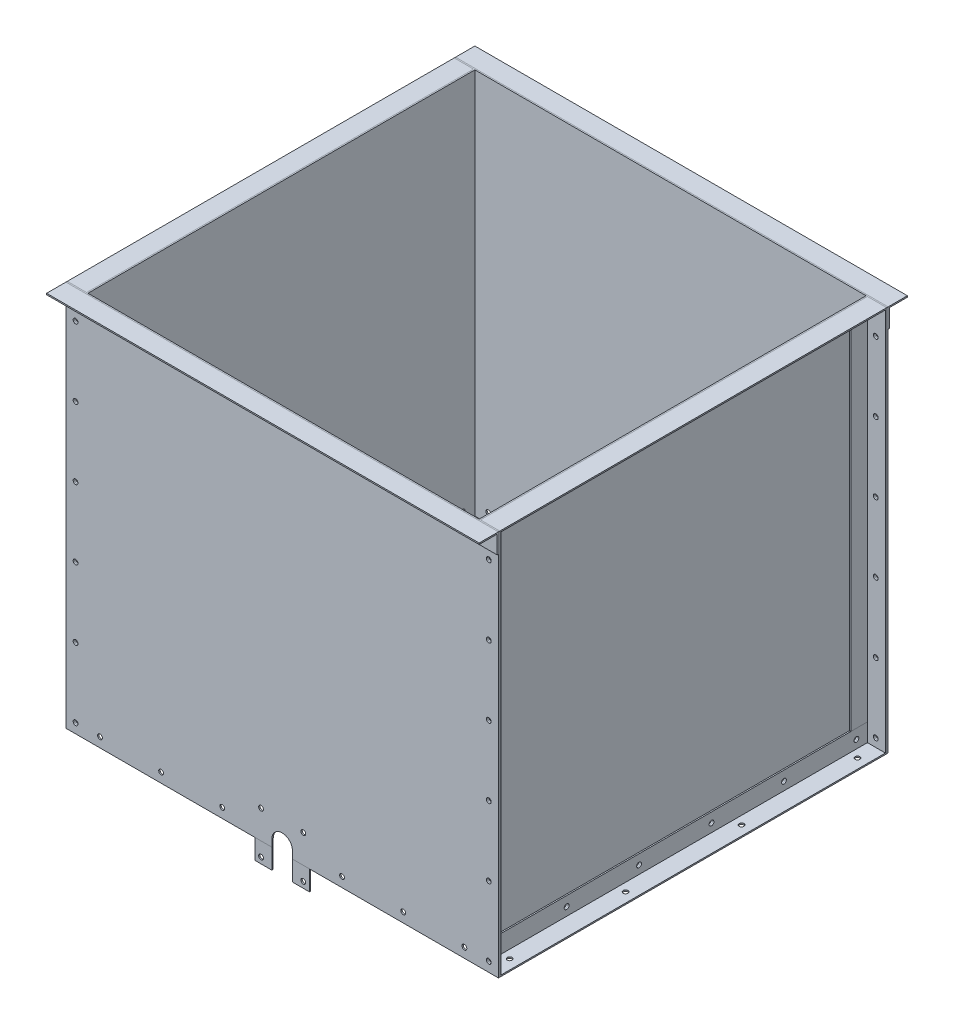
SolidWorks part; units mm, degrees
ref_plane "Plano frontal" through (0, 0, 0) normal (0, 0, 1) x (1, 0, 0)
ref_plane "Plano superior" through (0, 0, 0) normal (0, 1, 0) x (1, 0, 0)
ref_plane "Plano direito" through (0, 0, 0) normal (1, 0, 0) x (0, 0, -1)
sketch "Esboço1" plane through (0, 0, 0) normal (0, 0, 1) x (1, 0, 0)
  line L0 (0, 0) -> (0, 1227.36) construction
  line L1 (568.65, -19.05) -> (568.65, 996.95)
  line L2 (568.65, 996.95) -> (-568.65, 996.95)
  line L3 (568.65, -19.05) -> (27, -19.05)
  line L4 (-568.65, -19.05) -> (-568.65, 996.95)
  line L5 (-27, 0) -> (-27, -19.05)
  line L6 (27, 0) -> (27, -19.05)
  line L7 (543.25, 996.95) -> (543.25, -19.05) construction
  line L8 (-27, -19.05) -> (-568.65, -19.05)
  line L9 (-543.25, 996.95) -> (-543.25, -19.05) construction
  line L10 (543.25, 6.35) -> (-543.25, 6.35) construction
  arc A0 (27, 0) -> (-27, 0) centre (0, 0) ccw
  circle A1 centre (157.536, 6.35) radius 6.35
  circle A2 centre (318.318, 6.35) radius 6.35
  circle A3 centre (479.1, 6.35) radius 6.35
  circle A4 centre (-479.1, 6.35) radius 6.35
  circle A5 centre (-318.318, 6.35) radius 6.35
  circle A6 centre (-157.536, 6.35) radius 6.35
  circle A7 centre (543.25, 6.35) radius 6.35
  circle A8 centre (543.25, 189.23) radius 6.35
  circle A9 centre (543.25, 372.11) radius 6.35
  circle A10 centre (543.25, 554.99) radius 6.35
  circle A11 centre (543.25, 737.87) radius 6.35
  circle A12 centre (543.25, 920.75) radius 6.35
  circle A13 centre (-543.25, 920.75) radius 6.35
  circle A14 centre (-543.25, 737.87) radius 6.35
  circle A15 centre (-543.25, 554.99) radius 6.35
  circle A16 centre (-543.25, 372.11) radius 6.35
  circle A17 centre (-543.25, 189.23) radius 6.35
  circle A18 centre (-543.25, 6.35) radius 6.35
  dimension "D3" = 12.7
  dimension "D4" = 12.7
  dimension "D5" = 12.7
  dimension "D6" = 12.7
  dimension "D7" = 12.7
  dimension "D14" = 27
  dimension "D18" = 25.4
  dimension "D1" = 1016
  dimension "D2" = 25.4
  dimension "D8" = 182.88
  dimension "D9" = 182.88
  dimension "D10" = 182.88
  dimension "D11" = 182.88
  dimension "D12" = 182.88
  dimension "D13" = 19.05
  dimension "D15" = 19.05
  dimension "D16" = 19.05
  dimension "D17" = 568.65
  dimension "D19" = 25.4
  dimension "D20" = 64.15
  dimension "D21" = 224.932
  dimension "D22" = 385.714
base flange "Flange-base1" sketch "Esboço1" thickness 3.5 reverse thickness direction no parameters "D1"=6
pattern_linear "Padrão linear1" count 2 spacing 1021 along (0, 0, -1) of bodies 101
sketch "Esboço8" plane through (0, 996.95, 0) normal (0, 1, 0) x (1, 0, 0)
  line L0 (568.65, 1021) -> (-568.65, 1021) construction
  line L1 (517.85, 1021) -> (514.35, 1021)
  line L2 (517.85, 1021) -> (517.85, 3.5)
  line L3 (517.85, 3.5) -> (514.35, 3.5)
  line L4 (514.35, 1021) -> (514.35, 3.5)
  line L5 (568.65, 3.5) -> (-568.65, 3.5) construction
  line L6 (568.65, 3.5) -> (568.65, 0) construction
  line L7 (0, 0) -> (0, 1373.5489) construction
  line L8 (-514.35, 1021) -> (-514.35, 3.5)
  line L9 (-517.85, 3.5) -> (-514.35, 3.5)
  line L10 (-517.85, 1021) -> (-517.85, 3.5)
  line L11 (-517.85, 1021) -> (-514.35, 1021)
  dimension "D1" = 3.5
  dimension "D2" = 50.8
extrude "Ressalto-extrusão1" add sketch "Esboço8" against normal up to surface (1016 mm away) up to face at (297.825, -19.05, -1022.75)
sketch "Esboço11" plane through (0, 0, -1021) normal (0, 0, 1) x (1, 0, 0)
  line L0 (517.85, 31.75) -> (521.35, 31.75)
  line L1 (517.85, -19.05) -> (517.85, 996.95) construction
  line L2 (521.35, 31.75) -> (521.35, -15.55)
  line L3 (521.35, -15.55) -> (568.65, -15.55)
  line L4 (568.65, -19.05) -> (568.65, 996.95) construction
  line L5 (568.65, -15.55) -> (568.65, -19.05)
  line L6 (568.65, -19.05) -> (517.85, -19.05)
  line L7 (517.85, -19.05) -> (517.85, 31.75)
  dimension "D1" = 3.5
  dimension "D2" = 3.5
  dimension "D3" = 50.8
extrude "Ressalto-extrusão2" add sketch "Esboço11" along normal up to surface (1017.5 mm away) separate body up to face at (549.6, 920.75, -3.5)
sketch "Esboço12" plane through (521.35, 0, 0) normal (1, 0, 0) x (0, 0, -1)
  line L0 (512.25, 31.75) -> (512.25, -121.4216) construction
  line L1 (3.5, 31.75) -> (1021, 31.75) construction
  line L2 (3.5, 6.35) -> (1021, 6.35) construction
  line L4 (1021, -19.05) -> (1021, 996.95) construction
  line L5 (3.5, -19.05) -> (0, -19.05) construction
  circle A0 centre (417, 6.35) radius 6.35
  circle A1 centre (226.5, 6.35) radius 6.35
  circle A2 centre (36, 6.35) radius 6.35
  circle A3 centre (988.5, 6.35) radius 6.35
  circle A4 centre (798, 6.35) radius 6.35
  circle A5 centre (607.5, 6.35) radius 6.35
  dimension "D2" = 12.7
  dimension "D3" = 190.5
  dimension "D4" = 12.7
  dimension "D5" = 190.5
  dimension "D6" = 12.7
  dimension "D7" = 190.5
  dimension "D1" = 25.4
extrude "Corte-extrusão2" cut sketch "Esboço12" against normal blind 10
mirror "Espelhar2" about plane through (0, 0, 0) normal (1, 0, 0) of "Corte-extrusão2", "Ressalto-extrusão2"
sketch "Esboço13" plane through (0, 996.95, 0) normal (0, 1, 0) x (1, 0, 0)
  line L0 (568.65, 512.25) -> (-568.65, 512.25) construction
  line L1 (517.85, 1021) -> (521.35, 1021)
  line L2 (517.85, 1021) -> (517.85, 973.7)
  line L3 (517.85, 973.7) -> (521.35, 973.7)
  line L4 (521.35, 1021) -> (521.35, 973.7)
  line L5 (568.65, 3.5) -> (568.65, 1021) construction
  line L6 (-568.65, 3.5) -> (-568.65, 1021) construction
  line L7 (521.35, 3.5) -> (521.35, 50.8)
  line L8 (517.85, 50.8) -> (521.35, 50.8)
  line L9 (517.85, 3.5) -> (517.85, 50.8)
  line L10 (517.85, 3.5) -> (521.35, 3.5)
  dimension "D1" = 3.5
  dimension "D2" = 47.3
extrude "Ressalto-extrusão4" add sketch "Esboço13" against normal up to surface (965.2 mm away) separate body up to face at (519.6, 31.75, -512.25)
mirror "Espelhar3" about plane through (0, 0, 0) normal (1, 0, 0) of "Ressalto-extrusão4"
sketch "Esboço14" plane through (568.65, 0, 0) normal (1, 0, 0) x (0, 0, -1)
  line L0 (0, 996.95) -> (0, 946.15)
  line L1 (0, -19.05) -> (0, 996.95) construction
  line L2 (0, 996.95) -> (-50.8, 996.95)
  line L3 (-3.5, 993.45) -> (-3.5, 946.15)
  line L4 (-3.5, 993.45) -> (-50.8, 993.45)
  line L5 (0, 946.15) -> (-3.5, 946.15)
  line L6 (-50.8, 996.95) -> (-50.8, 993.45)
  dimension "D1" = 50.8
  dimension "D2" = 50.8
  dimension "D3" = 3.5
extrude "Ressalto-extrusão5" add sketch "Esboço14" against normal up to surface (1137.3 mm away) separate body up to face at (-568.65, 489.825, -512.25)
sketch "Esboço15" plane through (0, 0, -3.5) normal (0, 0, -1) x (-1, 0, 0)
  line L0 (-517.85, 996.95) -> (-568.65, 996.95)
  line L1 (-517.85, 996.95) -> (-517.85, 946.15)
  line L2 (-517.85, -19.05) -> (-517.85, 996.95) construction
  line L3 (568.65, 946.15) -> (-568.65, 946.15) construction
  line L4 (-517.85, 946.15) -> (-521.35, 946.15)
  line L5 (-521.35, 31.75) -> (-521.35, 996.95) construction
  line L6 (-521.35, 946.15) -> (-521.35, 993.45)
  line L7 (568.65, 993.45) -> (-568.65, 993.45) construction
  line L8 (-521.35, 993.45) -> (-568.65, 993.45)
  line L9 (-568.65, 993.45) -> (-568.65, 996.95)
extrude "Ressalto-extrusão6" add sketch "Esboço15" along normal up to surface (1017.5 mm away) separate body up to face at (549.6, 920.75, -1021)
sketch "Esboço16" plane through (521.35, 0, 0) normal (1, 0, 0) x (0, 0, -1)
  line L0 (1021, -19.05) -> (1021, 996.95) construction
  line L1 (3.5, 996.95) -> (1021, 996.95)
  line L2 (3.5, 996.95) -> (3.5, 946.15)
  line L3 (3.5, 946.15) -> (1021, 946.15)
  line L4 (1021, 996.95) -> (1021, 946.15)
  dimension "D1" = 50.8
extrude "Corte-extrusão3" cut sketch "Esboço16" against normal blind 3.5
sketch "Esboço17" plane through (-521.35, 0, 0) normal (-1, 0, 0) x (0, 0, 1)
  line L4 (-3.5, 996.95) -> (-1021, 996.95)
  line L5 (-1021, 996.95) -> (-1021, 946.15)
  line L6 (-1021, 946.15) -> (-3.5, 946.15)
  line L7 (-3.5, 946.15) -> (-3.5, 996.95)
  line L8 (-3.5, 996.95) -> (-1021, 996.95)
  line L9 (-1021, 996.95) -> (-1021, 946.15)
  line L10 (-1021, 946.15) -> (-3.5, 946.15)
  line L11 (-3.5, 946.15) -> (-3.5, 996.95)
  dimension "D1" = 0
extrude "Corte-extrusão4" cut sketch "Esboço17" against normal blind 3.5
mirror "Espelhar7" about plane through (0, 0, 0) normal (1, 0, 0) of bodies 115
ref_plane "Plano1" through (0, 0, -512.25) normal (0, 0, 1) x (1, 0, 0)
mirror "Espelhar8" about plane through (0, 0, -512.25) normal (0, 0, 1) of bodies 114
sketch "Esboço18" plane through (0, 0, -3.5) normal (0, 0, -1) x (-1, 0, 0)
  line L0 (-521.35, 993.45) -> (-568.65, 993.45)
  line L1 (-521.35, 993.45) -> (-521.35, -15.55)
  line L2 (-521.35, -15.55) -> (-521.35, 31.75) construction
  line L3 (-568.65, -15.55) -> (-521.35, -15.55)
  line L4 (-568.65, -19.05) -> (-517.85, -19.05)
  line L5 (-517.85, -19.05) -> (-517.85, 996.95)
  line L6 (-517.85, 996.95) -> (-568.65, 996.95)
  line L7 (-568.65, 996.95) -> (-568.65, -19.05)
  line L11 (-568.65, 993.45) -> (-568.65, -15.55)
  circle A0 centre (-543.25, 6.35) radius 6.35 construction
  circle A1 centre (-543.25, 189.23) radius 6.35 construction
  circle A2 centre (-543.25, 372.11) radius 6.35 construction
  circle A3 centre (-543.25, 554.99) radius 6.35 construction
  circle A4 centre (-543.25, 737.87) radius 6.35 construction
  circle A5 centre (-543.25, 920.75) radius 6.35 construction
  circle A6 centre (-543.25, 6.35) radius 6.35
  circle A7 centre (-543.25, 189.23) radius 6.35
  circle A8 centre (-543.25, 372.11) radius 6.35
  circle A9 centre (-543.25, 554.99) radius 6.35
  circle A10 centre (-543.25, 737.87) radius 6.35
  circle A11 centre (-543.25, 920.75) radius 6.35
  dimension "D1" = 0
extrude "Ressalto-extrusão7" add sketch "Esboço18" along normal blind 3.5 separate body
mirror "Espelhar9" about plane through (0, 0, -512.25) normal (0, 0, 1) of bodies 121
ref_plane "Plano2" through (0, 0, 0) normal (-1, 0, 0) x (0, 0, 1)
mirror "Espelhar10" about plane through (0, 0, 0) normal (-1, 0, 0) of bodies 121 122
sketch "Esboço19" plane through (0, -15.55, 0) normal (0, 1, 0) x (1, 0, 0)
  line L0 (-565.65, 359.849) -> (-520.85, 359.849) construction
  line L1 (0, 1089.75) -> (0, -570.8205) construction
  line L2 (25.4, 1089.75) -> (-25.4, 1089.75) construction
  circle A0 centre (-543.25, 969.45) radius 6.35
  circle A1 centre (-543.25, 664.651) radius 6.351
  circle A2 centre (-543.25, 359.849) radius 6.351
  circle A3 centre (-543.25, 55.05) radius 6.35
  circle A4 centre (543.25, 55.05) radius 6.35
  circle A5 centre (543.25, 359.849) radius 6.351
  circle A6 centre (543.25, 664.651) radius 6.351
  circle A7 centre (543.25, 969.45) radius 6.35
  dimension "D1" = 12.7
  dimension "D2" = 12.702
  dimension "D3" = 12.702
  dimension "D4" = 12.7
extrude "Corte-extrusão5" cut sketch "Esboço19" against normal up to surface (3.5 mm away) up to face at (543.25, -19.05, -512.25)
sketch "Esboço20" plane through (0, 0, 0) normal (0, 0, 1) x (1, 0, 0)
  circle A0 centre (-55.5623, 55.5623) radius 6.35
  circle A1 centre (55.5623, 55.5623) radius 6.35
  dimension "D1" = 12.7
  dimension "D2" = 12.7
extrude "Corte-extrusão6" cut sketch "Esboço20" against normal blind 10
sketch "Esboço22" plane through (0, 0, 0) normal (0, 0, 1) x (1, 0, 0)
  line L0 (0, 0) -> (0, -150.4853) construction
  line L1 (-568.65, -19.05) -> (-27, -19.05) construction
  line L2 (-71.4377, -19.05) -> (-27, -19.05)
  line L3 (-71.4377, -19.05) -> (-71.4377, -71.4377)
  line L4 (-71.4377, -71.4377) -> (-27, -71.4377)
  line L5 (71.4373, -19.05) -> (71.4373, -71.4377) construction
  line L6 (71.4373, 55.5623) -> (71.4373, -55.5627) construction
  line L8 (-71.4377, -55.5627) -> (-71.4377, 55.5623) construction
  line L9 (55.5623, -71.4377) -> (-55.5627, -71.4377) construction
  line L10 (27, -19.05) -> (27, -71.4377) construction
  line L11 (-27, -19.05) -> (-27, -71.4377)
  line L12 (27, -71.4377) -> (71.4373, -71.4377) construction
  line L13 (27, -19.05) -> (71.4373, -19.05) construction
  circle A0 centre (55.5623, -55.5627) radius 6.35 construction
  circle A1 centre (-55.5623, -55.5623) radius 6.35
  dimension "D1" = 12.7
  dimension "D2" = 12.7
base flange "Aba1" sketch "Esboço22" thickness 3.5 reverse thickness direction no parameters "D1"=6
mirror "Espelhar11" about plane through (0, 0, 0) normal (1, 0, 0) of bodies 129
mirror "Espelhar12" about plane through (0, 0, -512.25) normal (0, 0, 1) of bodies 129 130
sketch "Esboço31" plane through (0, 0, -1024.5) normal (0, 0, -1) x (-1, 0, 0)
  circle A0 centre (55.5625, 55.5625) radius 6.35
  circle A1 centre (-55.5625, 55.5625) radius 6.35
  dimension "D1" = 12.7
  dimension "D2" = 12.7
extrude "Corte-extrusão7" cut sketch "Esboço31" against normal up to surface (1024.5 mm away) up to face at (-49.2123, 55.5623, 0)
sketch "Curva-Linhas1" [suppressed] plane through (0, 0, 0) normal (0, 1, 0) x (1, 0, 0)
sketch "Caixa delimitadora1" [suppressed] plane through (0, 0, 0) normal (0, 1, 0) x (1, 0, 0)
sheet metal parameters "Chapa metálica1" thickness 3.5 parameters "D1"=6
flat pattern "Padrão-Plano1" [suppressed]
sketch "Curva-Linhas2" plane through (0, 0, 0) normal (0, 1, 0) x (1, 0, 0)
sketch3d "Caixa delimitadora2" [suppressed]
  line L0 (568.65, -19.05, 0) -> (-568.65, -19.05, 0) construction
  line L1 (568.65, 996.95, 0) -> (-568.65, 996.95, 0) construction
  line L2 (568.65, -19.05, 0) -> (568.65, 996.95, 0) construction
  line L3 (-568.65, -19.05, 0) -> (-568.65, 996.95, 0) construction
sheet metal parameters "Chapa metálica2" thickness 3.5 parameters "D1"=6
flat pattern "Padrão-Plano2"
sketch "Curva-Linhas3" plane through (0, 0, 0) normal (0, 1, 0) x (1, 0, 0)
sketch "Caixa delimitadora3" [suppressed] plane through (0, 0, 0) normal (0, 1, 0) x (1, 0, 0)
sheet metal parameters "Chapa metálica3" thickness 3.5 parameters "D1"=6
flat pattern "Padrão-Plano3"
sketch "Curva-Linhas4" plane through (0, 0, 0) normal (0, 1, 0) x (1, 0, 0)
sketch3d "Caixa delimitadora4" [suppressed]
  line L0 (-568.65, -19.05, 0) -> (568.65, -19.05, 0) construction
  line L1 (-568.65, 996.95, 0) -> (568.65, 996.95, 0) construction
  line L2 (-568.65, -19.05, 0) -> (-568.65, 996.95, 0) construction
  line L3 (568.65, -19.05, 0) -> (568.65, 996.95, 0) construction
sheet metal parameters "Chapa metálica4" thickness 3.5 parameters "D1"=6
flat pattern "Padrão-Plano3"
sketch "Curva-Linhas4" plane through (0, 0, 0) normal (0, 1, 0) x (1, 0, 0)
sketch3d "Caixa delimitadora4" [suppressed]
  line L0 (-568.65, -19.05, 0) -> (568.65, -19.05, 0) construction
  line L1 (-568.65, 996.95, 0) -> (568.65, 996.95, 0) construction
  line L2 (-568.65, -19.05, 0) -> (-568.65, 996.95, 0) construction
  line L3 (568.65, -19.05, 0) -> (568.65, 996.95, 0) construction
sheet metal parameters "Chapa metálica7" thickness 3.5 parameters "D1"=6
flat pattern "Padrão-Plano3"
sketch "Curva-Linhas4" plane through (0, 0, 0) normal (0, 1, 0) x (1, 0, 0)
sketch3d "Caixa delimitadora4" [suppressed]
  line L0 (-568.65, -19.05, 0) -> (568.65, -19.05, 0) construction
  line L1 (-568.65, 996.95, 0) -> (568.65, 996.95, 0) construction
  line L2 (-568.65, -19.05, 0) -> (-568.65, 996.95, 0) construction
  line L3 (568.65, -19.05, 0) -> (568.65, 996.95, 0) construction
sheet metal parameters "Chapa metálica9" thickness 3.5 parameters "D1"=6
flat pattern "Padrão-Plano3"
sketch "Curva-Linhas4" plane through (0, 0, 0) normal (0, 1, 0) x (1, 0, 0)
sketch3d "Caixa delimitadora4" [suppressed]
  line L0 (-568.65, -19.05, 0) -> (568.65, -19.05, 0) construction
  line L1 (-568.65, 996.95, 0) -> (568.65, 996.95, 0) construction
  line L2 (-568.65, -19.05, 0) -> (-568.65, 996.95, 0) construction
  line L3 (568.65, -19.05, 0) -> (568.65, 996.95, 0) construction
sheet metal parameters "Chapa metálica10" thickness 3.5 parameters "D1"=6
flat pattern "Padrão-Plano3"
sketch "Curva-Linhas4" plane through (0, 0, 0) normal (0, 1, 0) x (1, 0, 0)
sketch3d "Caixa delimitadora4" [suppressed]
  line L0 (-568.65, -19.05, 0) -> (568.65, -19.05, 0) construction
  line L1 (-568.65, 996.95, 0) -> (568.65, 996.95, 0) construction
  line L2 (-568.65, -19.05, 0) -> (-568.65, 996.95, 0) construction
  line L3 (568.65, -19.05, 0) -> (568.65, 996.95, 0) construction
sheet metal parameters "Chapa metálica13" thickness 3.5 parameters "D1"=6
flat pattern "Padrão-Plano3"
sketch "Curva-Linhas4" plane through (0, 0, 0) normal (0, 1, 0) x (1, 0, 0)
sketch3d "Caixa delimitadora4" [suppressed]
  line L0 (-568.65, -19.05, 0) -> (568.65, -19.05, 0) construction
  line L1 (-568.65, 996.95, 0) -> (568.65, 996.95, 0) construction
  line L2 (-568.65, -19.05, 0) -> (-568.65, 996.95, 0) construction
  line L3 (568.65, -19.05, 0) -> (568.65, 996.95, 0) construction
sheet metal parameters "Chapa metálica18" thickness 3.5 parameters "D1"=6
flat pattern "Padrão-Plano3"
sketch "Curva-Linhas4" plane through (0, 0, 0) normal (0, 1, 0) x (1, 0, 0)
sketch3d "Caixa delimitadora4" [suppressed]
  line L0 (-568.65, -19.05, 0) -> (568.65, -19.05, 0) construction
  line L1 (-568.65, 996.95, 0) -> (568.65, 996.95, 0) construction
  line L2 (-568.65, -19.05, 0) -> (-568.65, 996.95, 0) construction
  line L3 (568.65, -19.05, 0) -> (568.65, 996.95, 0) construction
sheet metal parameters "Chapa metálica21" thickness 3.5 parameters "D1"=6
flat pattern "Padrão-Plano3"
sketch "Curva-Linhas4" plane through (0, 0, 0) normal (0, 1, 0) x (1, 0, 0)
sketch3d "Caixa delimitadora4" [suppressed]
  line L0 (-568.65, -19.05, 0) -> (568.65, -19.05, 0) construction
  line L1 (-568.65, 996.95, 0) -> (568.65, 996.95, 0) construction
  line L2 (-568.65, -19.05, 0) -> (-568.65, 996.95, 0) construction
  line L3 (568.65, -19.05, 0) -> (568.65, 996.95, 0) construction
sheet metal parameters "Chapa metálica26" thickness 3.5 parameters "D1"=6
flat pattern "Padrão-Plano3"
sketch "Curva-Linhas4" plane through (0, 0, 0) normal (0, 1, 0) x (1, 0, 0)
sketch3d "Caixa delimitadora4" [suppressed]
  line L0 (-568.65, -19.05, 0) -> (568.65, -19.05, 0) construction
  line L1 (-568.65, 996.95, 0) -> (568.65, 996.95, 0) construction
  line L2 (-568.65, -19.05, 0) -> (-568.65, 996.95, 0) construction
  line L3 (568.65, -19.05, 0) -> (568.65, 996.95, 0) construction
sheet metal parameters "Chapa metálica27" thickness 3.5 parameters "D1"=6
flat pattern "Padrão-Plano3"
sketch "Curva-Linhas4" plane through (0, 0, 0) normal (0, 1, 0) x (1, 0, 0)
sketch3d "Caixa delimitadora4" [suppressed]
  line L0 (-568.65, -19.05, 0) -> (568.65, -19.05, 0) construction
  line L1 (-568.65, 996.95, 0) -> (568.65, 996.95, 0) construction
  line L2 (-568.65, -19.05, 0) -> (-568.65, 996.95, 0) construction
  line L3 (568.65, -19.05, 0) -> (568.65, 996.95, 0) construction
sheet metal parameters "Chapa metálica29" thickness 3.5 parameters "D1"=6
flat pattern "Padrão-Plano29"
sketch "Curva-Linhas5" plane through (0, 0, 0) normal (0, 1, 0) x (1, 0, 0)
sketch3d "Caixa delimitadora5" [suppressed]
  line L0 (27, -19.05, 0) -> (27, -71.4377, 0) construction
  line L1 (71.4377, -19.05, 0) -> (71.4377, -71.4377, 0) construction
  line L2 (27, -19.05, 0) -> (71.4377, -19.05, 0) construction
  line L3 (27, -71.4377, 0) -> (71.4377, -71.4377, 0) construction
sheet metal parameters "Chapa metálica30" thickness 3.5 parameters "D1"=6
flat pattern "Padrão-Plano30"
sketch "Curva-Linhas6" plane through (0, 0, 0) normal (0, 1, 0) x (1, 0, 0)
sketch "Caixa delimitadora6" [suppressed] plane through (0, 0, 0) normal (0, 1, 0) x (1, 0, 0)
sheet metal parameters "Chapa metálica31" thickness 3.5 parameters "D1"=6
flat pattern "Padrão-Plano31"
sketch "Curva-Linhas7" plane through (0, 0, 0) normal (0, 1, 0) x (1, 0, 0)
sketch "Caixa delimitadora7" [suppressed] plane through (0, 0, 0) normal (0, 1, 0) x (1, 0, 0)
sheet metal parameters "Chapa metálica32" thickness 3.5 parameters "D1"=6
flat pattern "Padrão-Plano32"
sketch "Curva-Linhas8" plane through (0, 0, 0) normal (0, 1, 0) x (1, 0, 0)
sketch "Caixa delimitadora8" [suppressed] plane through (0, 0, 0) normal (0, 1, 0) x (1, 0, 0)
sheet metal parameters "Chapa metálica33" thickness 3.5 parameters "D1"=6
flat pattern "Padrão-Plano3"
sketch "Curva-Linhas4" plane through (0, 0, 0) normal (0, 1, 0) x (1, 0, 0)
sketch3d "Caixa delimitadora4" [suppressed]
  line L0 (-568.65, -19.05, 0) -> (568.65, -19.05, 0) construction
  line L1 (-568.65, 996.95, 0) -> (568.65, 996.95, 0) construction
  line L2 (-568.65, -19.05, 0) -> (-568.65, 996.95, 0) construction
  line L3 (568.65, -19.05, 0) -> (568.65, 996.95, 0) construction
